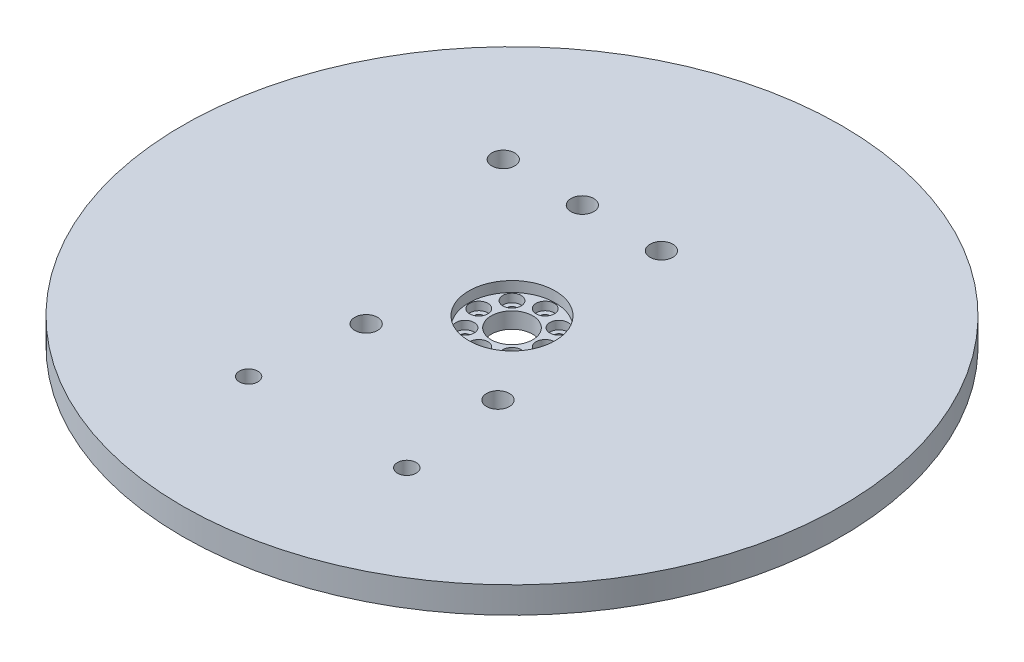
SolidWorks part; units mm, degrees
other "Markup1"
sketch "Sketch21" plane through (-65.5, -15.05, -60) normal (-0.0927, -0.2854, -0.9539) x (0.9951, -0.0609, -0.0785)
material "6061 Alloy"
ref_plane "Front Plane" through (0, 0, 0) normal (0, 0, 1) x (1, 0, 0)
ref_plane "Top Plane" through (0, 0, 0) normal (0, 1, 0) x (1, 0, 0)
ref_plane "Right Plane" through (0, 0, 0) normal (1, 0, 0) x (0, 0, -1)
sketch "Sketch1" plane through (0, 0, 0) normal (0, 1, 0) x (1, 0, 0)
  circle A0 centre (0, 0) radius 79.375
  dimension "D1" = 158.75
extrude "Boss-Extrude1" add sketch "Sketch1" along normal mid plane 6.35
sketch "Sketch2" plane through (0, -3.175, 0) normal (0, -1, 0) x (1, 0, 0)
  circle A0 centre (0, 0) radius 12.065
  circle A1 centre (0, 0) radius 79.375 construction
  dimension "D1" = 24.13
sketch "Sketch5" plane through (0, 3.175, 0) normal (0, 1, 0) x (1, 0, 0)
  circle A0 centre (0, 0) radius 10.4
  circle A1 centre (0, 0) radius 79.375 construction
  dimension "D1" = 20.8
extrude "Cut-Extrude1" cut sketch "Sketch5" against normal offset from surface (2.5 mm away) 2.5 up to face at (0, 3.175, 79.375)
sketch "Sketch6" plane through (0, 3.175, 0) normal (0, 1, 0) x (1, 0, 0)
  circle A0 centre (0, 0) radius 5
  circle A1 centre (0, 0) radius 10.4 construction
  dimension "D1" = 10
extrude "Cut-Extrude2" cut sketch "Sketch6" against normal through all
sketch "Sketch15" plane through (0, -3.175, 0) normal (0, 1, 0) x (1, 0, 0)
  circle A0 centre (0, 8) radius 1
  circle A1 centre (-5.6569, 5.6569) radius 1
  circle A2 centre (5.6569, 5.6569) radius 1
  circle A3 centre (-5.6569, -5.6569) radius 1
  circle A4 centre (5.6569, -5.6569) radius 1
  circle A5 centre (-8, 0) radius 1
  circle A6 centre (0, -8) radius 1
  circle A7 centre (8, 0) radius 1
  circle A8 centre (0, 0) radius 4
  circle A9 centre (0, 0) radius 11
  circle A10 centre (0, 0) radius 2.25
  circle A11 centre (0, 0) radius 5
  circle A12 centre (0, 0) radius 5 construction
  point P2 (-8.8764, -0.571)
  point P24 (0, 0)
  dimension "D1" = 4.5
  dimension "D2" = 8
  dimension "D3" = 10
  dimension "D4" = 22
  dimension "D5" = 2
  dimension "D6" = 8
  dimension "D7" = 5.6569
  dimension "D8" = 8
  dimension "D9" = 5.6569
  dimension "D10" = 5.6569
  dimension "D11" = 8
  dimension "D12" = 5.6569
  dimension "D13" = 8
hole_wizard "CBORE for M2 SHCS1" positions "Sketch19" profile "Sketch20" counterbore size "M2" standard "ANSI Metric"
sketch "Sketch19" plane through (0, 0.675, 0) normal (0, 1, 0) x (1, 0, 0)
  point P0 (-5.6569, 5.6569)
  point P3 (0, 8)
  point P6 (5.6569, 5.6569)
  point P9 (8, 0)
  point P12 (5.6569, -5.6569)
  point P15 (0, -8)
  point P18 (-5.6569, -5.6569)
  point P21 (-8, 0)
sketch "Sketch20" plane through (-5.6569, 0.675, -5.6569) normal (1, 0, 0) x (0, 0, 1)
  line L0 (0, 0) -> (0, 6.6609)
  line L1 (0, 6.6609) -> (1.1, 6)
  line L2 (1.1, 6) -> (1.1, 2)
  line L3 (1.1, 2) -> (2.2, 2)
  line L4 (2.2, 2) -> (2.2, 0)
  line L5 (2.2, 0) -> (0, 0)
  line L10 (0, 6.6609) -> (-1.1, 6) construction
  line L11 (0, -6.35) -> (0, 107.95) construction
  dimension "Hole Dia." = 2.2
  dimension "Hole Depth" = 6
  dimension "C'Bore Dia." = 4.4
  dimension "C'Bore Depth" = 2
  dimension "Drill Angle" = 118
hole_wizard "M4 Clearance Hole1" positions "Sketch22" profile "Sketch23" hole size "M4" standard "ANSI Metric" end condition through all
sketch "Sketch22" plane through (0, 3.175, 0) normal (0, 1, 0) x (1, 0, 0)
  point P0 (19.05, -44.3882)
  point P3 (-19.05, -44.3882)
sketch "Sketch23" plane through (19.05, 3.175, 44.3882) normal (1, 0, 0) x (0, 0, 1)
  line L0 (0, 0) -> (0, 6.35)
  line L1 (0, 6.35) -> (2.25, 6.35)
  line L2 (2.25, 6.35) -> (2.25, 0)
  line L5 (2.25, 0) -> (0, 0)
  line L11 (0, -6.35) -> (0, 107.95) construction
  dimension "Thru Hole Dia." = 4.5
  dimension "Thru Hole Depth" = 6.35
hole_wizard "M5 Clearance Hole1" positions "Sketch24" profile "Sketch25" hole size "M5" standard "ANSI Metric" end condition through all
sketch "Sketch24" plane through (0, 3.175, 0) normal (0, 1, 0) x (1, 0, 0)
  point P0 (-33.6688, 31.5674)
  point P3 (-14.6188, 31.5674)
  point P6 (4.4312, 31.5674)
  point P9 (-15.875, -19.2497)
  point P12 (15.875, -19.2497)
sketch "Sketch25" plane through (-33.6688, 3.175, -31.5674) normal (1, 0, 0) x (0, 0, 1)
  line L0 (0, 0) -> (0, 6.35)
  line L1 (0, 6.35) -> (2.75, 6.35)
  line L2 (2.75, 6.35) -> (2.75, 0)
  line L5 (2.75, 0) -> (0, 0)
  line L11 (0, -6.35) -> (0, 107.95) construction
  dimension "Thru Hole Dia." = 5.5
  dimension "Thru Hole Depth" = 6.35
